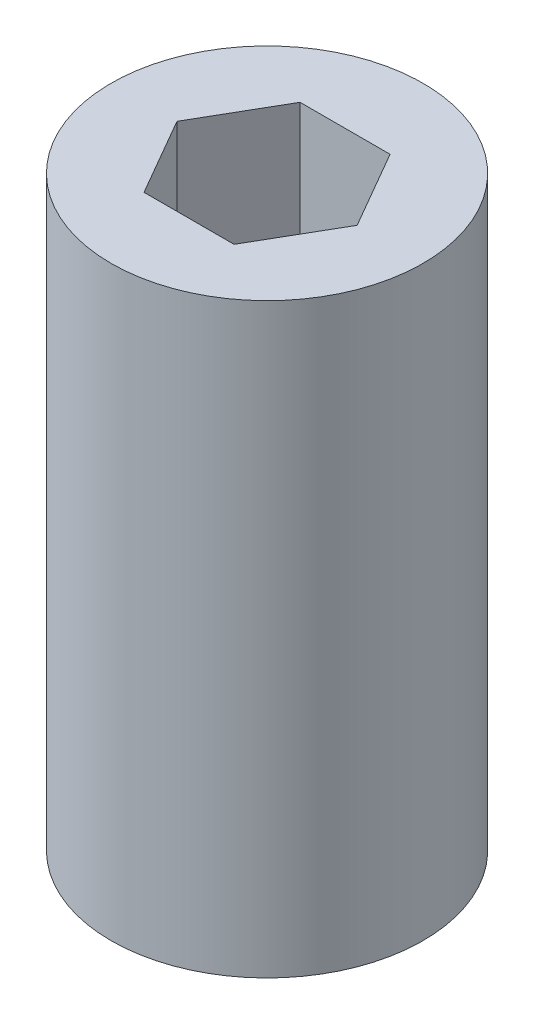
SolidWorks part; units mm, degrees
ref_plane "Front Plane" through (0, 0, 0) normal (0, 0, 1) x (1, 0, 0)
ref_plane "Top Plane" through (0, 0, 0) normal (0, 1, 0) x (1, 0, 0)
ref_plane "Right Plane" through (0, 0, 0) normal (1, 0, 0) x (0, 0, -1)
sketch "Sketch1" plane through (0, 0, 0) normal (0, 1, 0) x (1, 0, 0)
  line L1 (3.6662, -6.35) -> (7.3323, 0)
  line L2 (7.3323, 0) -> (3.6662, 6.35)
  line L3 (3.6662, 6.35) -> (-3.6662, 6.35)
  line L4 (-3.6662, 6.35) -> (-7.3323, 0)
  line L5 (-7.3323, 0) -> (-3.6662, -6.35)
  line L6 (-3.6662, -6.35) -> (3.6662, -6.35)
  circle A0 centre (0, 0) radius 6.35 construction
  circle A1 centre (0, 0) radius 12.7
  dimension "D2" = 25.4
  dimension "D1" = 12.7
extrude "Boss-Extrude1" add sketch "Sketch1" along normal blind 47.752
